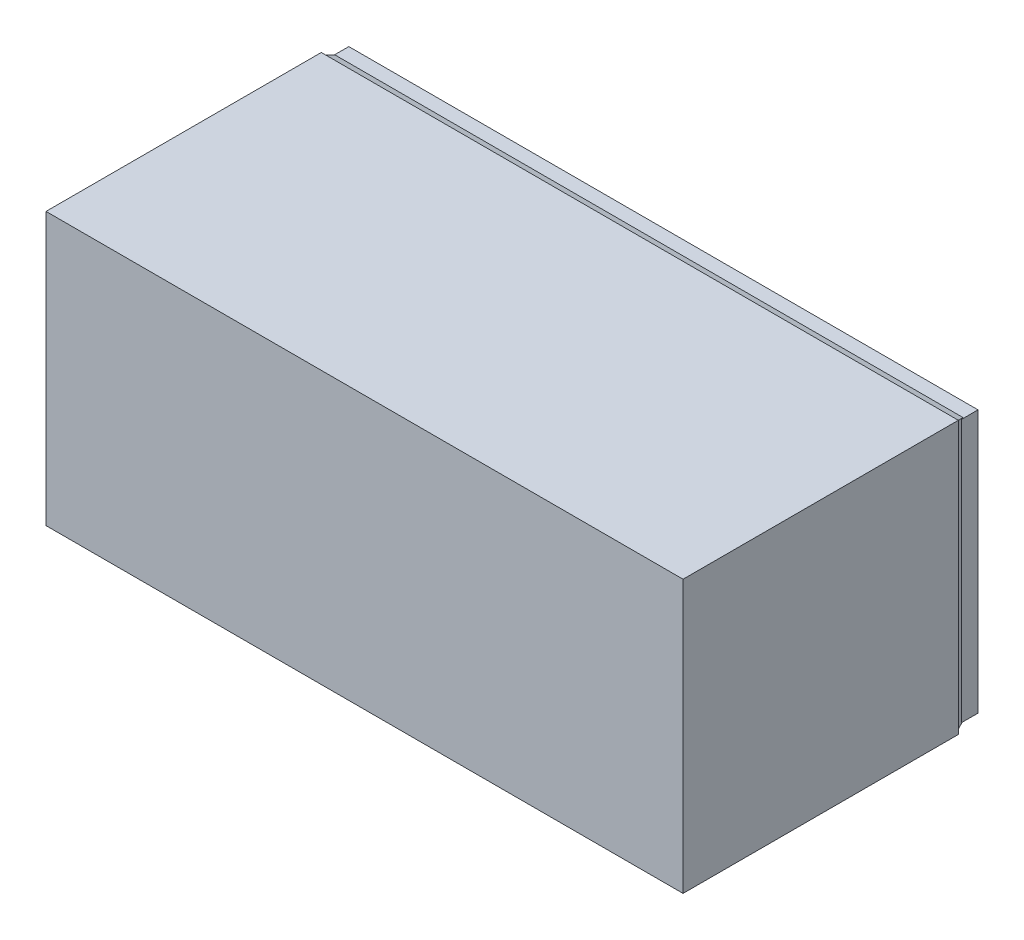
SolidWorks part; units mm, degrees
ref_plane "前视基准面" through (0, 0, 0) normal (0, 0, 1) x (1, 0, 0)
ref_plane "上视基准面" through (0, 0, 0) normal (0, 1, 0) x (1, 0, 0)
ref_plane "右视基准面" through (0, 0, 0) normal (1, 0, 0) x (0, 0, -1)
sketch "草图1" plane through (0, 0, 0) normal (0, 0, 1) x (1, 0, 0)
  line L0 (-528.8018, 0) -> (528.8018, 0) construction
  line L1 (0, -42.9111) -> (0, 186.1291) construction
  line L3 (0, 0) -> (405, 0)
  line L4 (0, 0) -> (0, 173)
  line L5 (0, 173) -> (405, 173)
  line L6 (405, 0) -> (405, 173)
  dimension "D1" = 405
  dimension "D2" = 173
extrude "凸台-拉伸1" add sketch "草图1" along normal blind 190
sketch "草图2" plane through (0, 0, 0) normal (0, 0, -1) x (-1, 0, 0)
  line L0 (-202.5, 173) -> (-202.5, 0) construction
  line L1 (-405, 173) -> (0, 173) construction
  line L2 (0, 0) -> (-405, 0) construction
  line L3 (-405, 86.5) -> (0, 86.5) construction
  line L4 (-405, 0) -> (-405, 173) construction
  line L5 (0, 173) -> (0, 0) construction
  line L7 (-405, 0) -> (0, 0)
  line L8 (-405, 0) -> (-405, 173)
  line L9 (-405, 173) -> (0, 173)
  line L10 (0, 0) -> (0, 173)
  line L11 (-405, 0) -> (0, 173) construction
  line L12 (-405, 173) -> (0, 0) construction
  line L13 (-402.5, 3) -> (-2.5, 3)
  line L14 (-402.5, 3) -> (-402.5, 170)
  line L15 (-402.5, 170) -> (-2.5, 170)
  line L16 (-2.5, 3) -> (-2.5, 170)
  line L17 (-402.5, 3) -> (-2.5, 170) construction
  line L18 (-402.5, 170) -> (-2.5, 3) construction
  point P12 (-202.5, 86.5)
  point P18 (-202.5, 86.5)
  dimension "D1" = 167
  dimension "D2" = 400
extrude "切除-拉伸1" cut sketch "草图2" against normal blind 9
sketch "草图3" plane through (0, 0, 0) normal (0, -1, 0) x (1, 0, 0)
  line L0 (405, 190) -> (405, 9) construction
  line L1 (0, 9) -> (405, 9)
  line L2 (0, 9) -> (0, 15)
  line L3 (0, 15) -> (405, 15)
  line L4 (405, 9) -> (405, 15)
  line L5 (402.5, 0) -> (2.5, 0) construction
  dimension "D1" = 15
extrude "切除-拉伸2" cut sketch "草图3" against normal blind 1
sketch "草图4" plane through (405, 0, 0) normal (1, 0, 0) x (0, 0, -1)
  line L1 (-9, 173) -> (-15, 173)
  line L2 (-9, 173) -> (-9, 0)
  line L3 (-9, 0) -> (-15, 0)
  line L4 (-15, 173) -> (-15, 0)
extrude "切除-拉伸3" cut sketch "草图4" against normal blind 1
sketch "草图5" plane through (0, 173, 0) normal (0, 1, 0) x (1, 0, 0)
  line L1 (0, -9) -> (404, -9)
  line L2 (0, -9) -> (0, -15)
  line L3 (0, -15) -> (404, -15)
  line L4 (404, -9) -> (404, -15)
extrude "切除-拉伸4" cut sketch "草图5" against normal blind 1
sketch "草图6" plane through (0, 0, 0) normal (-1, 0, 0) x (0, 0, 1)
  line L1 (9, 172) -> (15, 172)
  line L2 (9, 172) -> (9, 1)
  line L3 (9, 1) -> (15, 1)
  line L4 (15, 172) -> (15, 1)
extrude "切除-拉伸5" cut sketch "草图6" against normal blind 1
chamfer "倒角1" distance 2 distance2 6 2 edges at (1, 86.5, 9) (404, 86.5, 9) first distance on face at (202.5, 86.5, 9)
chamfer "倒角2" distance 2 distance2 6 2 edges at (202.5, 172, 9) (202.5, 1, 9) first distance on face at (202.5, 171, 9) first distance on face at (202.5, 2, 9)
sketch "草图7" plane through (0, 0, 0) normal (0, 0, -1) x (-1, 0, 0)
  line L0 (-202.5, 170) -> (-202.5, 1) construction
  line L1 (-2.5, 170) -> (-402.5, 170) construction
  line L2 (-404, 1) -> (-1, 1) construction
  line L3 (-402.5, 86.5) -> (-2.5, 86.5) construction
  line L4 (-402.5, 170) -> (-402.5, 3) construction
  line L5 (-2.5, 3) -> (-2.5, 170) construction
  line L6 (-402.5, 3) -> (-2.5, 3) construction
  line L7 (-268.036, 168.3) -> (-203.35, 168.3)
  line L8 (-268.036, 168.3) -> (-268.036, 4.7)
  line L9 (-268.036, 4.7) -> (-203.35, 4.7)
  line L10 (-203.35, 168.3) -> (-203.35, 4.7)
  line L11 (-201.65, 168.3) -> (-136.964, 168.3)
  line L12 (-201.65, 168.3) -> (-201.65, 4.7)
  line L13 (-201.65, 4.7) -> (-136.964, 4.7)
  line L14 (-136.964, 168.3) -> (-136.964, 4.7)
  line L15 (-135.264, 168.3) -> (-70.582, 168.3)
  line L16 (-135.264, 168.3) -> (-135.264, 4.7)
  line L17 (-135.264, 4.7) -> (-70.582, 4.7)
  line L18 (-70.582, 168.3) -> (-70.582, 4.7)
  line L19 (-68.882, 168.3) -> (-4.2, 168.3)
  line L20 (-68.882, 168.3) -> (-68.882, 4.7)
  line L21 (-68.882, 4.7) -> (-4.2, 4.7)
  line L22 (-4.2, 168.3) -> (-4.2, 4.7)
  line L23 (-334.418, 168.3) -> (-269.736, 168.3)
  line L24 (-334.418, 168.3) -> (-334.418, 4.7)
  line L25 (-334.418, 4.7) -> (-269.736, 4.7)
  line L26 (-269.736, 168.3) -> (-269.736, 4.7)
  line L27 (-400.8, 168.3) -> (-336.118, 168.3)
  line L28 (-400.8, 168.3) -> (-400.8, 4.7)
  line L29 (-400.8, 4.7) -> (-336.118, 4.7)
  line L30 (-336.118, 168.3) -> (-336.118, 4.7)
  line L31 (-402, 3) -> (-3, 3) construction
  dimension "D1" = 0.85
  dimension "D2" = 1.7
  dimension "D3" = 1.7
  dimension "D4" = 1.7
  dimension "D5" = 1.7
  dimension "D6" = 1.7
  dimension "D7" = 1.7
  dimension "D8" = 1.7
  dimension "D9" = 1.7
  dimension "D10" = 1.7
  dimension "D11" = 1.7
  dimension "D12" = 1.7
  dimension "D13" = 1.7
  dimension "D14" = 1.7
  dimension "D15" = 1.7
  dimension "D16" = 1.7
  dimension "D17" = 64.682
  dimension "D18" = 64.682
  dimension "D19" = 1.7
  dimension "D20" = 1.7
  dimension "D21" = 1.7
  dimension "D22" = 1.7
  dimension "D23" = 64.682
  dimension "D24" = 64.682
extrude "切除-拉伸6" cut sketch "草图7" against normal blind 183
ref_plane "基准面1" through (202.5, 0, 0) normal (-1, 0, 0) x (0, 0, 1)
ref_plane "基准面2" through (0, 86.5, 0) normal (0, 1, 0) x (1, 0, 0)
